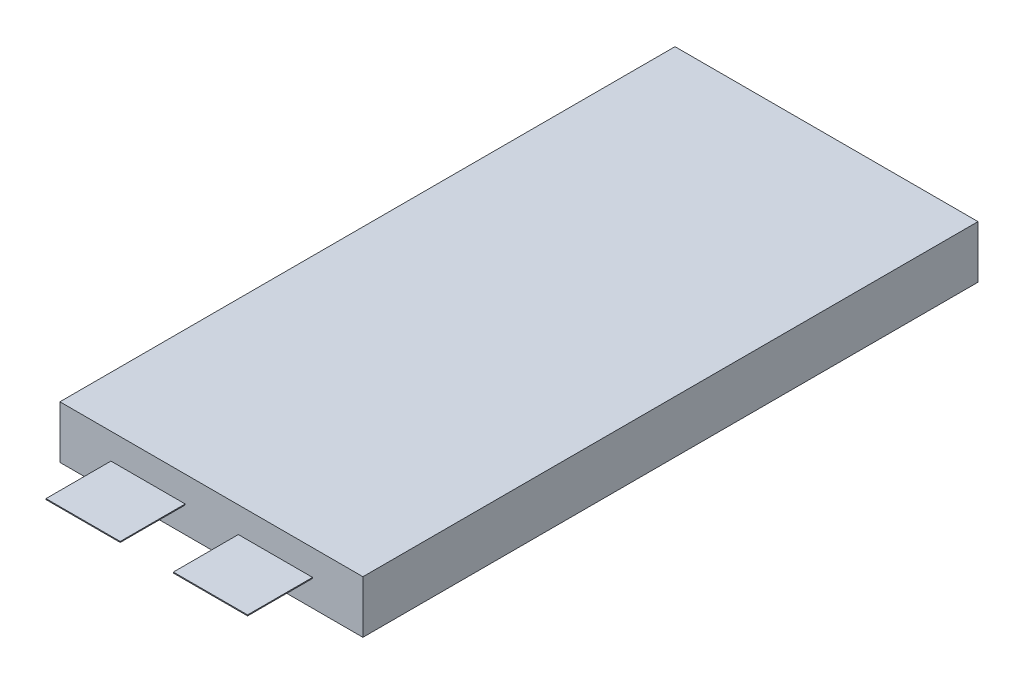
SolidWorks part; units mm, degrees
ref_plane "Front" through (0, 0, 0) normal (0, 0, 1) x (1, 0, 0)
ref_plane "Top" through (0, 0, 0) normal (0, 1, 0) x (1, 0, 0)
ref_plane "Right" through (0, 0, 0) normal (1, 0, 0) x (0, 0, -1)
sketch "Sketch1" plane through (0, 0, 0) normal (0, 0, 1) x (1, 0, 0)
  line L1 (-20.6742, 1.7083) -> (11.9858, 1.7083)
  line L2 (-20.6742, 1.7083) -> (-20.6742, -3.9517)
  line L3 (-20.6742, -3.9517) -> (11.9858, -3.9517)
  line L4 (11.9858, 1.7083) -> (11.9858, -3.9517)
  dimension "D1" = 32.66
  dimension "D2" = 5.66
extrude "Boss-Extrude1" add sketch "Sketch1" along normal blind 66.3
sketch3d "3DSketch1"
  line L0 (-20.6742, 1.7083, 66.3) -> (-20.6742, -3.9517, 66.3) construction
  line L1 (-20.6742, -1.1217, 66.3) -> (-15.1742, -1.1217, 66.3) construction
  line L2 (-4.3442, -1.1217, 66.3) -> (-1.4442, -1.1217, 66.3) construction
  line L4 (-4.3442, 1.7083, 66.3) -> (-4.3442, -3.9517, 66.3) construction
  line L6 (-15.1742, -1.1217, 66.3) -> (-4.3442, -1.1217, 66.3) construction
  line L7 (-15.1742, -1.1217, 66.3) -> (-7.1742, -1.1217, 66.3) construction
  line L8 (6.5558, -1.0684, 66.3) -> (-1.4442, -1.0684, 66.3) construction
  line L10 (-15.1742, -1.1784, 66.3) -> (-7.1742, -1.1784, 66.3)
  line L11 (-15.1742, -1.1784, 66.3) -> (-15.1742, -1.0784, 66.3)
  line L12 (-15.1742, -1.0784, 66.3) -> (-7.1742, -1.0784, 66.3)
  line L13 (-7.1742, -1.1784, 66.3) -> (-7.1742, -1.0784, 66.3)
  line L14 (-15.1742, -1.1784, 66.3) -> (-7.1742, -1.0784, 66.3) construction
  line L15 (-15.1742, -1.0784, 66.3) -> (-7.1742, -1.1784, 66.3) construction
  line L16 (-1.4442, -1.1726, 66.3) -> (6.5558, -1.1707, 66.3)
  line L17 (-1.4442, -1.1726, 66.3) -> (-1.4442, -1.0707, 66.3)
  line L18 (-1.4442, -1.0707, 66.3) -> (6.5558, -1.0687, 66.3)
  line L19 (6.5558, -1.1707, 66.3) -> (6.5558, -1.0687, 66.3)
  line L20 (-1.4442, -1.1726, 66.3) -> (6.5558, -1.0687, 66.3) construction
  line L21 (-1.4442, -1.0707, 66.3) -> (6.5558, -1.1707, 66.3) construction
  point P5 (0, 0, 0)
  point P6 (-11.1742, -1.1217, 66.3)
  point P15 (-11.1742, -1.1784, 66.3)
  point P16 (-1.4442, -1.1217, 66.3)
  point P18 (2.5558, -1.0684, 66.3)
  point P25 (2.5558, -1.0684, 66.3)
  dimension "D1" = 8
  dimension "D2" = 0.1
  dimension "D4" = 0.1
  dimension "D3" = 8
extrude "Boss-Extrude3" add sketch "3DSketch1" along direction (0, 0, -1) on the side against the normal blind 7
sketch3d "3DSketch2"
  line L1 (-14.0004, -3.9517, 62.7689) -> (-8.8677, -3.9517, 62.7689)
  line L2 (-14.0004, -3.9517, 62.7689) -> (-14.0004, -3.9517, 63.1495)
  line L3 (-14.0004, -3.9517, 63.1495) -> (-8.8677, -3.9517, 63.1495)
  line L4 (-8.8677, -3.9517, 62.7689) -> (-8.8677, -3.9517, 63.1495)
  line L5 (-14.0004, -3.9517, 62.7689) -> (-8.8677, -3.9517, 63.1495) construction
  line L6 (-14.0004, -3.9517, 63.1495) -> (-8.8677, -3.9517, 62.7689) construction
  circle A0 centre (-11.434, -3.9517, 62.9592) radius 2.9324
  circle A1 centre (-11.434, -3.9517, 62.9592) radius 3.0862
  point P2 (-11.434, -6.8841, 62.9592)
  point P8 (-11.434, -7.0378, 62.9592)
extrude "Cut-Extrude1" cut sketch "3DSketch2" along direction (0, -1, 0) on the side of the normal blind 0.1
